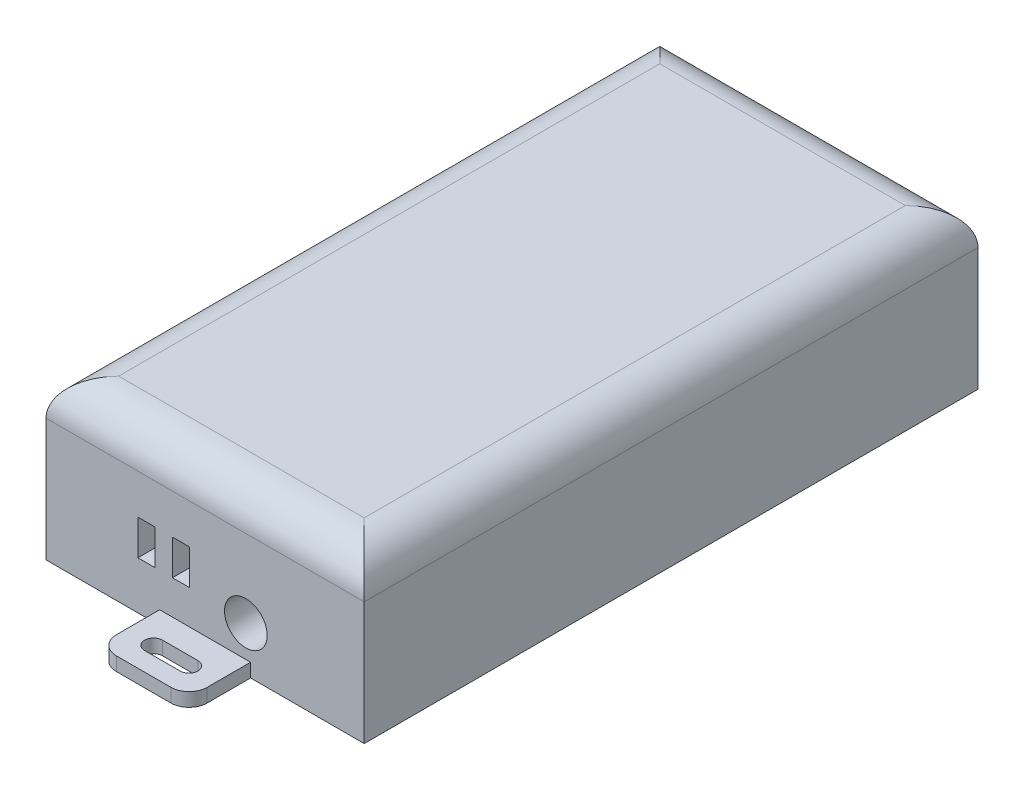
SolidWorks part; units mm, degrees
ref_plane "Front Plane" through (0, 0, 0) normal (0, 0, 1) x (1, 0, 0)
ref_plane "Top Plane" through (0, 0, 0) normal (0, 1, 0) x (1, 0, 0)
ref_plane "Right Plane" through (0, 0, 0) normal (1, 0, 0) x (0, 0, -1)
sketch "Sketch1" plane through (0, 0, 0) normal (0, 1, 0) x (1, 0, 0)
  line L1 (0, 0) -> (44.45, 0)
  line L2 (0, 0) -> (0, 85.725)
  line L3 (0, 85.725) -> (44.45, 85.725)
  line L4 (44.45, 0) -> (44.45, 85.725)
  dimension "D1" = 44.45
  dimension "D2" = 85.725
extrude "Boss-Extrude1" add sketch "Sketch1" along normal blind 22.225
fillet "Fillet1" radius 5.08 4 edges at (22.225, 22.225, -85.725) (44.45, 22.225, -42.8625) (22.225, 22.225, 0) (0, 22.225, -42.8625)
sketch "Sketch2" plane through (0, 0, 0) normal (0, 0, 1) x (1, 0, 0)
  circle A0 centre (27.9151, 6.2942) radius 2.9815
extrude "Cut-Extrude1" cut sketch "Sketch2" against normal blind 12.7
sketch "Sketch3" plane through (0, 0, 0) normal (0, 0, 1) x (1, 0, 0)
  line L1 (12.838, 11.5871) -> (15.2257, 11.5871)
  line L2 (12.838, 11.5871) -> (12.838, 6.6724)
  line L3 (12.838, 6.6724) -> (15.2257, 6.6724)
  line L4 (15.2257, 11.5871) -> (15.2257, 6.6724)
  line L5 (17.6657, 11.5871) -> (20.0535, 11.5871)
  line L6 (17.6657, 11.5871) -> (17.6657, 6.6724)
  line L7 (17.6657, 6.6724) -> (20.0535, 6.6724)
  line L8 (20.0535, 11.5871) -> (20.0535, 6.6724)
extrude "Cut-Extrude2" cut sketch "Sketch3" against normal blind 7.62
sketch "Sketch4" plane through (0, 0, -85.725) normal (0, 0, -1) x (-1, 0, 0)
  line L0 (-27.4959, 9.5518) -> (-26.2003, 9.5518) construction
  line L1 (-30.8234, 9.5518) -> (-27.4959, 9.5518)
  line L2 (-30.8234, 9.5518) -> (-30.8234, 4.1926)
  line L3 (-30.8234, 4.1926) -> (-27.4959, 4.1926)
  line L4 (-27.4959, 9.5518) -> (-27.4959, 4.1926)
  line L5 (-26.2003, 9.5518) -> (-22.8728, 9.5518)
  line L6 (-26.2003, 9.5518) -> (-26.2003, 4.1926)
  line L7 (-26.2003, 4.1926) -> (-22.8728, 4.1926)
  line L8 (-22.8728, 9.5518) -> (-22.8728, 4.1926)
  line L9 (-21.5772, 9.5518) -> (-18.2497, 9.5518)
  line L10 (-21.5772, 9.5518) -> (-21.5772, 4.1926)
  line L11 (-21.5772, 4.1926) -> (-18.2497, 4.1926)
  line L12 (-18.2497, 9.5518) -> (-18.2497, 4.1926)
  line L13 (-16.9541, 9.5518) -> (-13.6266, 9.5518)
  line L14 (-16.9541, 9.5518) -> (-16.9541, 4.1926)
  line L15 (-16.9541, 4.1926) -> (-13.6266, 4.1926)
  line L16 (-13.6266, 9.5518) -> (-13.6266, 4.1926)
  line L17 (-22.8728, 9.5518) -> (-21.5772, 9.5518) construction
  line L18 (-18.2497, 9.5518) -> (-16.9541, 9.5518) construction
  line L19 (-44.45, 0) -> (0, 0) construction
  point P25 (-22.225, 0)
  point P26 (-22.225, 9.5518)
extrude "Cut-Extrude3" cut sketch "Sketch4" against normal blind 7.62
sketch "Sketch5" plane through (0, 0, 0) normal (0, -1, 0) x (1, 0, 0)
  line L0 (15.875, 0) -> (15.875, 6.0583)
  line L1 (0, 0) -> (44.45, 0) construction
  line L2 (18.415, 8.5983) -> (26.035, 8.5983)
  line L3 (28.575, 6.0583) -> (28.575, 0)
  line L4 (15.875, 0) -> (28.575, 0)
  line L7 (19.7514, 5.9847) -> (24.6986, 5.9847)
  line L8 (24.6986, 3.4764) -> (19.7514, 3.4764)
  arc A0 (26.035, 8.5983) -> (28.575, 6.0583) centre (26.035, 6.0583) cw
  arc A1 (18.415, 8.5983) -> (15.875, 6.0583) centre (18.415, 6.0583) ccw
  arc A4 (24.6986, 5.9847) -> (24.6986, 3.4764) centre (24.6986, 4.7305) cw
  arc A5 (19.7514, 3.4764) -> (19.7514, 5.9847) centre (19.7514, 4.7305) cw
  point P7 (22.225, 8.5983)
  point P8 (22.225, 0)
  point P18 (22.225, 5.9847)
  dimension "D1" = 2.54
  dimension "D3" = 12.7
extrude "Boss-Extrude2" add sketch "Sketch5" against normal blind 1.905
ref_point "Point1"
ref_plane "Plane3" through (0, 0, -41.7898) normal (0, 0, 1) x (1, 0, 0)
mirror "Mirror2" about plane through (0, 0, -41.7898) normal (0, 0, 1) of "Boss-Extrude2"
